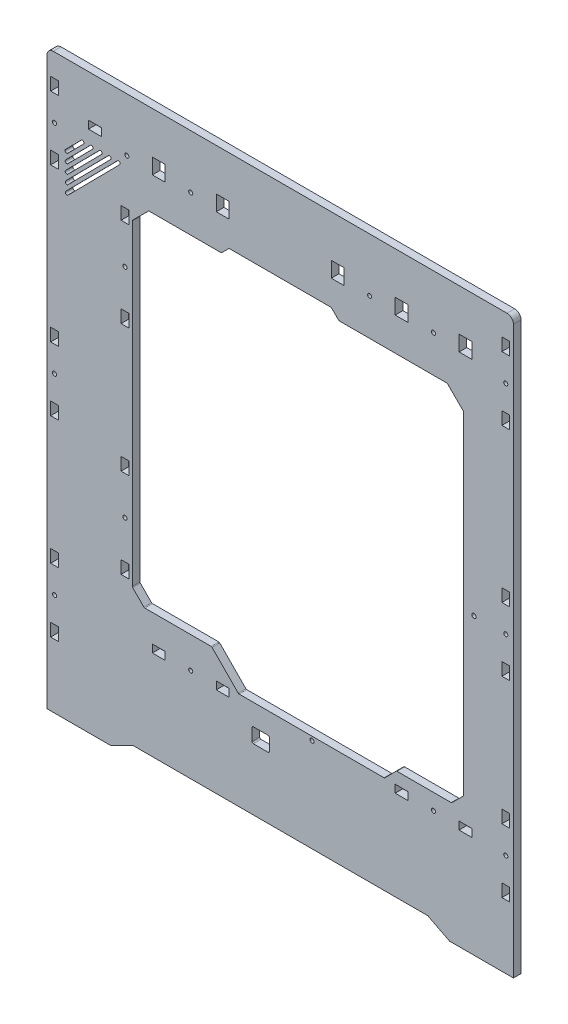
SolidWorks part; units mm, degrees
material "Клен"
ref_plane "Front" through (0, 0, 0) normal (0, 0, 1) x (1, 0, 0)
ref_plane "Top" through (0, 0, 0) normal (0, 1, 0) x (1, 0, 0)
ref_plane "Right" through (0, 0, 0) normal (1, 0, 0) x (0, 0, -1)
sketch "Эскиз1" plane through (0, 0, 0) normal (0, 0, 1) x (1, 0, 0)
  line L0 (830.5087, 490.0072) -> (773.3665, 490.0072)
  line L1 (768.3665, 485.0072) -> (768.3665, 477.0072)
  line L8 (1124.3665, 292.0072) -> (1130.4665, 292.0072)
  line L9 (1124.3665, 302.0072) -> (1124.3665, 292.0072)
  line L10 (1130.4665, 302.0072) -> (1124.3665, 302.0072)
  line L11 (1130.4665, 292.0072) -> (1130.4665, 302.0072)
  line L32 (1133.3665, 42.0072) -> (1133.3665, 477.0072)
  line L39 (909.8665, 490.0072) -> (830.5087, 490.0072)
  line L42 (768.3665, 477.0072) -> (768.3665, 42.0072)
  line L43 (768.3665, 42.0072) -> (818.3665, 42.0072)
  line L44 (818.3665, 42.0072) -> (835.3665, 50.7375)
  line L45 (835.3665, 50.7375) -> (1066.3665, 50.7375)
  line L46 (1066.3665, 50.7375) -> (1083.3665, 42.0072)
  line L47 (1083.3665, 42.0072) -> (1133.3665, 42.0072)
  line L48 (1124.3665, 242.0072) -> (1130.4665, 242.0072)
  line L49 (1124.3665, 252.0072) -> (1124.3665, 242.0072)
  line L50 (1130.4665, 252.0072) -> (1124.3665, 252.0072)
  line L51 (1130.4665, 242.0072) -> (1130.4665, 252.0072)
  line L56 (1124.3665, 142.0072) -> (1130.4665, 142.0072)
  line L57 (1124.3665, 152.0072) -> (1124.3665, 142.0072)
  line L58 (1130.4665, 152.0072) -> (1124.3665, 152.0072)
  line L59 (1130.4665, 142.0072) -> (1130.4665, 152.0072)
  line L64 (1124.3665, 92.0072) -> (1130.4665, 92.0072)
  line L65 (1124.3665, 102.0072) -> (1124.3665, 92.0072)
  line L66 (1130.4665, 102.0072) -> (1124.3665, 102.0072)
  line L67 (1130.4665, 92.0072) -> (1130.4665, 102.0072)
  line L72 (1100.8665, 127.1049) -> (1090.8665, 127.1049)
  line L73 (1100.8665, 121.0049) -> (1100.8665, 127.1049)
  line L74 (1090.8665, 121.0049) -> (1100.8665, 121.0049)
  line L75 (1090.8665, 127.1049) -> (1090.8665, 121.0049)
  line L80 (1050.8665, 127.1049) -> (1040.8665, 127.1049)
  line L81 (1050.8665, 121.0049) -> (1050.8665, 127.1049)
  line L82 (1040.8665, 121.0049) -> (1050.8665, 121.0049)
  line L83 (1040.8665, 127.1049) -> (1040.8665, 121.0049)
  line L88 (941.3665, 110.5049) -> (929.8665, 110.5049)
  line L89 (942.3665, 100.0049) -> (942.3665, 109.5049)
  line L90 (929.8665, 99.0049) -> (941.3665, 99.0049)
  line L91 (928.8665, 109.5049) -> (928.8665, 100.0049)
  line L96 (910.8665, 121.0049) -> (910.8665, 127.1049)
  line L97 (900.8665, 121.0049) -> (910.8665, 121.0049)
  line L98 (900.8665, 127.1049) -> (900.8665, 121.0049)
  line L99 (910.8665, 127.1049) -> (900.8665, 127.1049)
  line L104 (860.8665, 121.0049) -> (860.8665, 127.1049)
  line L105 (850.8665, 121.0049) -> (860.8665, 121.0049)
  line L106 (850.8665, 127.1049) -> (850.8665, 121.0049)
  line L107 (860.8665, 127.1049) -> (850.8665, 127.1049)
  line L112 (771.2665, 102.0072) -> (771.2665, 92.0072)
  line L113 (777.3665, 102.0072) -> (771.2665, 102.0072)
  line L114 (777.3665, 92.0072) -> (777.3665, 102.0072)
  line L115 (771.2665, 92.0072) -> (777.3665, 92.0072)
  line L120 (771.2665, 152.0072) -> (771.2665, 142.0072)
  line L121 (777.3665, 152.0072) -> (771.2665, 152.0072)
  line L122 (777.3665, 142.0072) -> (777.3665, 152.0072)
  line L123 (771.2665, 142.0072) -> (777.3665, 142.0072)
  line L128 (826.3665, 172.0072) -> (826.3665, 162.0072)
  line L129 (832.4665, 172.0072) -> (826.3665, 172.0072)
  line L130 (832.4665, 162.0072) -> (832.4665, 172.0072)
  line L131 (826.3665, 162.0072) -> (832.4665, 162.0072)
  line L136 (826.3665, 242.0072) -> (826.3665, 232.0072)
  line L137 (832.4665, 242.0072) -> (826.3665, 242.0072)
  line L138 (832.4665, 232.0072) -> (832.4665, 242.0072)
  line L139 (826.3665, 232.0072) -> (832.4665, 232.0072)
  line L144 (771.2665, 252.0072) -> (771.2665, 242.0072)
  line L145 (777.3665, 252.0072) -> (771.2665, 252.0072)
  line L146 (777.3665, 242.0072) -> (777.3665, 252.0072)
  line L147 (771.2665, 242.0072) -> (777.3665, 242.0072)
  line L152 (1124.3665, 412.0072) -> (1130.4665, 412.0072)
  line L153 (1124.3665, 422.0072) -> (1124.3665, 412.0072)
  line L154 (1130.4665, 422.0072) -> (1124.3665, 422.0072)
  line L155 (1130.4665, 412.0072) -> (1130.4665, 422.0072)
  line L160 (1124.3665, 462.0072) -> (1130.4665, 462.0072)
  line L161 (1124.3665, 472.0072) -> (1124.3665, 462.0072)
  line L162 (1130.4665, 472.0072) -> (1124.3665, 472.0072)
  line L163 (1130.4665, 462.0072) -> (1130.4665, 472.0072)
  line L168 (1090.8665, 457.1072) -> (1090.8665, 445.0072)
  line L169 (1100.8665, 457.1072) -> (1090.8665, 457.1072)
  line L170 (1100.8665, 445.0072) -> (1100.8665, 457.1072)
  line L171 (1090.8665, 445.0072) -> (1100.8665, 445.0072)
  line L176 (1040.8665, 457.1072) -> (1040.8665, 445.0072)
  line L177 (1050.8665, 457.1072) -> (1040.8665, 457.1072)
  line L178 (1050.8665, 445.0072) -> (1050.8665, 457.1072)
  line L179 (1040.8665, 445.0072) -> (1050.8665, 445.0072)
  line L184 (990.8665, 457.1072) -> (990.8665, 445.0072)
  line L185 (1000.8665, 457.1072) -> (990.8665, 457.1072)
  line L186 (1000.8665, 445.0072) -> (1000.8665, 457.1072)
  line L187 (990.8665, 445.0072) -> (1000.8665, 445.0072)
  line L192 (900.8665, 445.0072) -> (910.8665, 445.0072)
  line L193 (900.8665, 457.1072) -> (900.8665, 445.0072)
  line L194 (910.8665, 457.1072) -> (900.8665, 457.1072)
  line L195 (910.8665, 445.0072) -> (910.8665, 457.1072)
  line L200 (826.3665, 412.0072) -> (826.3665, 402.0072)
  line L201 (832.4665, 412.0072) -> (826.3665, 412.0072)
  line L202 (832.4665, 402.0072) -> (832.4665, 412.0072)
  line L203 (826.3665, 402.0072) -> (832.4665, 402.0072)
  line L224 (996.2808, 419.7551) -> (991.4523, 424.5835)
  line L225 (1081.1223, 419.1693) -> (997.695, 419.1693)
  line L226 (1094.1201, 406.6723) -> (1081.8269, 418.8789)
  line L227 (1094.4155, 146.42) -> (1094.4155, 405.9627)
  line L228 (1085.3572, 136.8536) -> (1094.1263, 145.7167)
  line L229 (1042.289, 136.5569) -> (1084.6463, 136.5569)
  line L230 (1032.8134, 127.4016) -> (1041.5781, 136.2603)
  line L231 (918.729, 127.1049) -> (1032.1025, 127.1049)
  line L232 (897.5745, 148.2016) -> (918.0158, 127.4039)
  line L233 (844.9385, 148.5006) -> (896.8613, 148.5006)
  line L234 (835.4584, 157.6604) -> (844.2276, 148.7973)
  line L235 (835.1693, 405.9627) -> (835.1693, 158.3637)
  line L236 (847.7579, 418.8789) -> (835.4647, 406.6723)
  line L237 (904.0381, 419.1693) -> (848.4625, 419.1693)
  line L238 (910.2808, 424.5835) -> (905.4523, 419.7551)
  line L239 (990.0381, 425.1693) -> (911.695, 425.1693)
  line L240 (850.8665, 445.0072) -> (860.8665, 445.0072)
  line L241 (850.8665, 457.1072) -> (850.8665, 445.0072)
  line L242 (860.8665, 457.1072) -> (850.8665, 457.1072)
  line L243 (860.8665, 445.0072) -> (860.8665, 457.1072)
  line L244 (784.8721, 398.2711) -> (825.3055, 439.1538)
  line L245 (823.528, 440.9118) -> (783.0946, 400.0291)
  line L248 (784.8331, 405.3421) -> (818.2346, 439.1147)
  line L249 (816.4571, 440.8727) -> (783.0556, 407.1001)
  line L252 (784.794, 412.4131) -> (811.1636, 439.0757)
  line L253 (809.3861, 440.8336) -> (783.0165, 414.171)
  line L256 (784.7549, 419.484) -> (804.0927, 439.0366)
  line L257 (802.3151, 440.7946) -> (782.9774, 421.242)
  line L260 (784.7159, 426.555) -> (797.0217, 438.9975)
  line L261 (795.2442, 440.7555) -> (782.9384, 428.313)
  line L262 (909.8665, 490.0072) -> (1128.3665, 490.0072)
  line L263 (1133.3665, 485.0072) -> (1133.3665, 477.0072)
  line L268 (771.2665, 422.0072) -> (771.2665, 412.0072)
  line L269 (777.3665, 422.0072) -> (771.2665, 422.0072)
  line L270 (777.3665, 412.0072) -> (777.3665, 422.0072)
  line L271 (771.2665, 412.0072) -> (777.3665, 412.0072)
  line L276 (800.8665, 451.0072) -> (810.8665, 451.0072)
  line L277 (800.8665, 457.1072) -> (800.8665, 451.0072)
  line L278 (810.8665, 457.1072) -> (800.8665, 457.1072)
  line L279 (810.8665, 451.0072) -> (810.8665, 457.1072)
  line L284 (771.2665, 472.0072) -> (771.2665, 462.0072)
  line L285 (777.3665, 472.0072) -> (771.2665, 472.0072)
  line L286 (777.3665, 462.0072) -> (777.3665, 472.0072)
  line L287 (771.2665, 462.0072) -> (777.3665, 462.0072)
  line L292 (826.3665, 342.0072) -> (826.3665, 332.0072)
  line L293 (832.4665, 342.0072) -> (826.3665, 342.0072)
  line L294 (832.4665, 332.0072) -> (832.4665, 342.0072)
  line L295 (826.3665, 332.0072) -> (832.4665, 332.0072)
  line L300 (771.2665, 302.0072) -> (771.2665, 292.0072)
  line L301 (777.3665, 302.0072) -> (771.2665, 302.0072)
  line L302 (777.3665, 292.0072) -> (777.3665, 302.0072)
  line L303 (771.2665, 292.0072) -> (777.3665, 292.0072)
  arc A0 (1128.3665, 490.0072) -> (1133.3665, 485.0072) centre (1128.3665, 485.0072) cw
  circle A2 centre (1127.4165, 272.0072) radius 1.6
  circle A4 centre (1102.521, 272.0072) radius 1.7
  circle A6 centre (1127.4165, 122.0072) radius 1.6
  arc A23 (773.3665, 482.0072) -> (768.3665, 477.0072) centre (773.3665, 477.0072) ccw
  circle A24 centre (1070.8665, 124.0549) radius 1.6
  circle A26 centre (975.8665, 124.0549) radius 1.6
  circle A28 centre (880.8665, 124.0549) radius 1.6
  arc A34 (929.8665, 110.5049) -> (928.8665, 109.5049) centre (929.8665, 109.5049) ccw
  arc A35 (942.3665, 109.5049) -> (941.3665, 110.5049) centre (941.3665, 109.5049) ccw
  arc A36 (941.3665, 99.0049) -> (942.3665, 100.0049) centre (941.3665, 100.0049) ccw
  arc A37 (928.8665, 100.0049) -> (929.8665, 99.0049) centre (929.8665, 100.0049) ccw
  circle A38 centre (774.3165, 122.0072) radius 1.6
  circle A40 centre (829.4165, 202.0072) radius 1.6
  circle A42 centre (774.3165, 272.0072) radius 1.6
  circle A44 centre (1127.4165, 442.0072) radius 1.6
  circle A46 centre (1070.8665, 448.0572) radius 1.6
  circle A48 centre (1020.8665, 448.0572) radius 1.6
  circle A50 centre (880.8665, 448.0572) radius 1.6
  circle A52 centre (830.8665, 448.0572) radius 1.6
  arc A56 (825.3055, 439.1538) -> (823.528, 440.9118) centre (824.4168, 440.0328) ccw
  arc A57 (783.0946, 400.0291) -> (784.8721, 398.2711) centre (783.9834, 399.1501) ccw
  arc A60 (818.2346, 439.1147) -> (816.4571, 440.8727) centre (817.3458, 439.9937) ccw
  arc A61 (783.0556, 407.1001) -> (784.8331, 405.3421) centre (783.9443, 406.2211) ccw
  arc A64 (811.1636, 439.0757) -> (809.3861, 440.8336) centre (810.2749, 439.9546) ccw
  arc A65 (783.0165, 414.171) -> (784.794, 412.4131) centre (783.9053, 413.292) ccw
  arc A82 (991.4523, 424.5835) -> (990.0381, 425.1693) centre (990.0381, 423.1693) ccw
  arc A83 (996.2808, 419.7551) -> (997.695, 419.1693) centre (997.695, 421.1693) ccw
  arc A84 (1081.8269, 418.8789) -> (1081.1223, 419.1693) centre (1081.1223, 418.1693) ccw
  arc A85 (1094.4155, 405.9627) -> (1094.1201, 406.6723) centre (1093.4155, 405.9627) ccw
  arc A86 (1094.1263, 145.7167) -> (1094.4155, 146.42) centre (1093.4155, 146.42) ccw
  arc A87 (1084.6463, 136.5569) -> (1085.3572, 136.8536) centre (1084.6463, 137.5569) ccw
  arc A88 (1042.289, 136.5569) -> (1041.5781, 136.2603) centre (1042.289, 135.5569) ccw
  arc A89 (1032.1025, 127.1049) -> (1032.8134, 127.4016) centre (1032.1025, 128.1049) ccw
  arc A90 (918.0158, 127.4039) -> (918.729, 127.1049) centre (918.729, 128.1049) ccw
  arc A91 (897.5745, 148.2016) -> (896.8613, 148.5006) centre (896.8613, 147.5006) ccw
  arc A92 (844.2276, 148.7973) -> (844.9385, 148.5006) centre (844.9385, 149.5006) ccw
  arc A93 (835.1693, 158.3637) -> (835.4584, 157.6604) centre (836.1693, 158.3637) ccw
  arc A94 (835.4647, 406.6723) -> (835.1693, 405.9627) centre (836.1693, 405.9627) ccw
  arc A95 (848.4625, 419.1693) -> (847.7579, 418.8789) centre (848.4625, 418.1693) ccw
  arc A96 (904.0381, 419.1693) -> (905.4523, 419.7551) centre (904.0381, 421.1693) ccw
  arc A97 (911.695, 425.1693) -> (910.2808, 424.5835) centre (911.695, 423.1693) ccw
  arc A100 (804.0927, 439.0366) -> (802.3151, 440.7946) centre (803.2039, 439.9156) ccw
  arc A101 (782.9774, 421.242) -> (784.7549, 419.484) centre (783.8662, 420.363) ccw
  arc A104 (797.0217, 438.9975) -> (795.2442, 440.7555) centre (796.1329, 439.8765) ccw
  arc A105 (782.9384, 428.313) -> (784.7159, 426.555) centre (783.8271, 427.434) ccw
  circle A106 centre (774.3165, 442.0072) radius 1.6
  circle A108 centre (829.4165, 372.0072) radius 1.6
  arc A109 (773.3665, 490.0072) -> (768.3665, 485.0072) centre (773.3665, 485.0072) ccw
  dimension "D51" = 5
extrude "Бобышка-Вытянуть1" add sketch "Эскиз1" along normal blind 6 contours L0 A109 L1 L42 L43 L44 L45 L46 L47 L32 L263 A0 L262 L39 L11 L8 L9 L10 L51 L48 L49 L50 L59 L56 L57 L58 L67 L64 L65 L66 L75 L72 L73 L74 L83 L80 L81 L82 L99 L96 L97 L98 region at (870.1876, 484.2286, 0)
